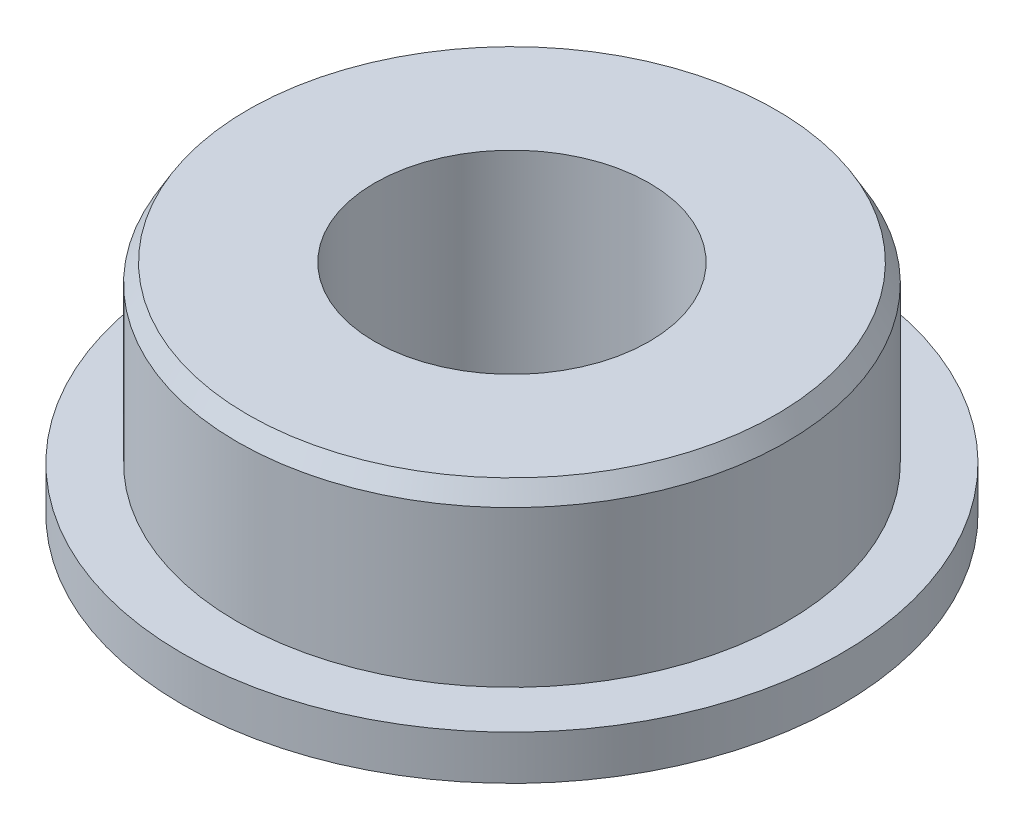
SolidWorks part; units mm, degrees
material "AISI 1045 钢，冷拔"
ref_plane "前视基准面" through (0, 0, 0) normal (0, 0, 1) x (1, 0, 0)
ref_plane "上视基准面" through (0, 0, 0) normal (0, 1, 0) x (1, 0, 0)
ref_plane "右视基准面" through (0, 0, 0) normal (1, 0, 0) x (0, 0, -1)
sketch "草图1" plane through (0, 0, 0) normal (0, 1, 0) x (1, 0, 0)
  circle A0 centre (0, 0) radius 1.5
  circle A1 centre (0, 0) radius 3
  circle A2 centre (0, 0) radius 3.6
  dimension "d" = 3
  dimension "D " = 6
  dimension "法兰外径" = 7.2
extrude "凸台-拉伸1" add sketch "草图1" along normal blind 2.5 contours A1 A0 region at (-2.9151, 0, 0)
extrude "凸台-拉伸2" add sketch "草图1<3>" along normal blind 0.6 contours A2 A1 region at (-3.4982, 0, 0)
sketch "草图1<3>" plane through (0, 0, 0) normal (0, 1, 0) x (1, 0, 0) same geometry as "草图1"
chamfer "倒角1" distance 0.2 angle 30 2 edges at (0, 2.5, 3) (0, 0, 3.6) first distance on face at (0, 0.6, 3) first distance on face at (0, 0, 1.5)
